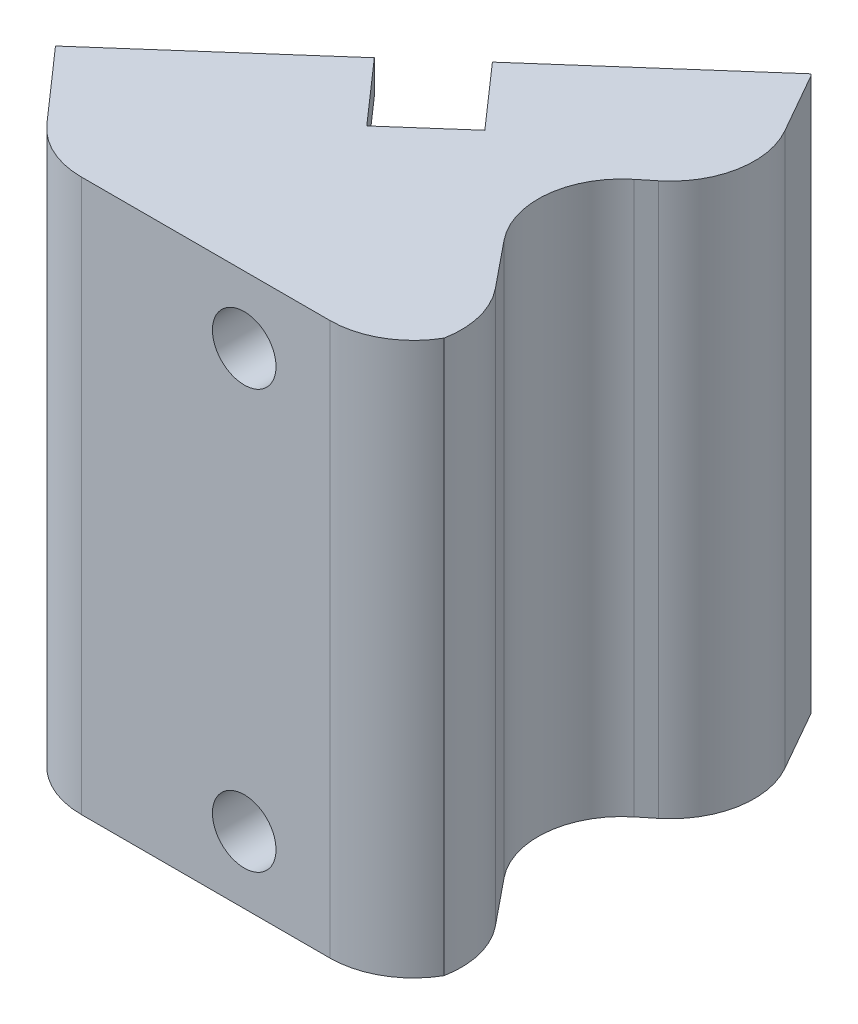
SolidWorks part; units mm, degrees
ref_plane "Front Plane" through (0, 0, 0) normal (0, 0, 1) x (1, 0, 0)
ref_plane "Top Plane" through (0, 0, 0) normal (0, 1, 0) x (1, 0, 0)
ref_plane "Right Plane" through (0, 0, 0) normal (1, 0, 0) x (0, 0, -1)
sketch "Sketch1" plane through (0, 0, 0) normal (0, 1, 0) x (1, 0, 0)
  line L0 (0, 0) -> (20, 0)
  line L1 (20, 0) -> (30.1598, 17.5974)
  line L2 (20, 0) -> (-2.3608, 38.73) construction
  line L3 (0, 0) -> (24.022, 21.141)
  line L4 (30.1598, 17.5974) -> (24.022, 21.141)
  line L5 (20, 0) -> (11.2706, 9.9189) construction
  dimension "D1" = 120
  dimension "D2" = 20
  dimension "D3" = 32
  dimension "D4" = 60
  dimension "D5" = 90
  dimension "D6" = 11.35
extrude "Boss-Extrude1" add sketch "Sketch1" along normal blind 33
sketch "Sketch2" plane through (0, 0, 0) normal (0.6607, 0, 0.7507) x (0.7507, 0, -0.6607)
  line L1 (0, 0) -> (32, 0)
  line L2 (0, 0) -> (0, 33)
  line L3 (0, 33) -> (32, 33)
  line L4 (32, 0) -> (32, 33)
extrude "Boss-Extrude2" add sketch "Sketch2" against normal blind 3
sketch "Sketch3" plane through (30, 0, 0) normal (0, 0, -1) x (-1, 0, 0)
  line L0 (18, -986.4883) -> (18, 49013.5117) construction
  line L1 (-972.5, 16.5) -> (49027.5, 16.5) construction
  line L3 (30, 33) -> (30, 0) construction
  line L4 (30, 33) -> (10, 33) construction
  circle A0 centre (18, 29) radius 1.9
  circle A1 centre (18, 4) radius 1.9
  dimension "D2" = 3.8
  dimension "D3" = 3.8
  dimension "D1" = 12
  dimension "D4" = 12.5
  dimension "D5" = 12.5
  dimension "D6" = 16.5
extrude "Cut-Extrude1" cut sketch "Sketch3" along normal blind 7
fillet "Fillet1" radius 5 1 edges at (20, 16.5, 0)
sketch "Sketch5" plane through (-1.982, 0, -2.2521) normal (-0.6607, 0, -0.7507) x (-0.7507, 0, 0.6607)
  line L0 (-32, 16.5) -> (0, 16.5) construction
  line L3 (-16, 33) -> (-16, 0) construction
  line L8 (0, 33) -> (0, 0) construction
  line L9 (-32, 33) -> (0, 33) construction
  line L10 (0, 0) -> (-32, 0) construction
  line L11 (-32, 33) -> (-32, 0) construction
  circle A0 centre (-28.3, 28.4) radius 2
  circle A1 centre (-3.7, 28.4) radius 2
  circle A2 centre (-28.3, 4.6) radius 2
  circle A3 centre (-3.7, 4.6) radius 2
  dimension "D6" = 4
  dimension "D7" = 4
  dimension "D8" = 4
  dimension "D9" = 4
  dimension "D1" = 12.3
  dimension "D2" = 12.3
  dimension "D3" = 12.3
  dimension "D4" = 12.3
  dimension "D5" = 11.9
  dimension "D10" = 11.9
  dimension "D11" = 11.9
  dimension "D12" = 11.9
extrude "Boss-Extrude3" add sketch "Sketch5" along normal blind 5
sketch "Sketch6" plane through (-1.982, 0, -2.2521) normal (-0.6607, 0, -0.7507) x (-0.7507, 0, 0.6607)
  line L0 (-2, 2) -> (-2, 31)
  line L1 (0, 0) -> (-32, 0)
  line L2 (0, 0) -> (0, 33)
  line L3 (0, 33) -> (-32, 33)
  line L4 (-32, 0) -> (-32, 33)
  line L5 (-2, 31) -> (-30, 31)
  line L6 (-30, 2) -> (-30, 31)
  line L7 (-2, 2) -> (-30, 2)
  dimension "D1" = 2
extrude "Boss-Extrude4" add sketch "Sketch6" along normal blind 5
sketch "Sketch9" plane through (-1.982, 0, -2.2521) normal (-0.6607, 0, -0.7507) x (-0.7507, 0, 0.6607)
  line L0 (-28.3, 26.4) -> (-30, 26.4)
  line L3 (-30, 27.3464) -> (-30, 5.6536) construction
  line L5 (-30, 26.4) -> (-30, 31)
  line L7 (-30, 31) -> (-26.3, 31)
  line L8 (-2, 31) -> (-30, 31) construction
  line L9 (-26.3, 31) -> (-26.3, 28.4)
  line L10 (-26.3, 28.4) -> (-28.3, 26.4)
  line L11 (-5.7, 28.4) -> (-5.7, 31)
  line L13 (-5.7, 31) -> (-2, 31)
  line L14 (-2, 31) -> (-2, 26.4)
  line L15 (-2, 5.6536) -> (-2, 27.3464) construction
  line L17 (-2, 26.4) -> (-3.7, 26.4)
  line L18 (-3.7, 26.4) -> (-5.7, 28.4)
  line L20 (-3.7, 6.6) -> (-2, 6.6)
  line L21 (-2, 5.6536) -> (-2, 27.3464) construction
  line L22 (-2, 6.6) -> (-2, 2)
  line L24 (-2, 2) -> (-5.7, 2)
  line L25 (-30, 2) -> (-2, 2) construction
  line L27 (-5.7, 2) -> (-5.7, 4.6)
  line L28 (-5.7, 4.6) -> (-3.7, 6.6)
  line L29 (-28.3, 6.6) -> (-30, 6.6)
  line L30 (-30, 6.6) -> (-30, 2)
  line L31 (-30, 2) -> (-26.3, 2)
  line L32 (-26.3, 2) -> (-26.3, 4.6)
  line L33 (-26.3, 4.6) -> (-28.3, 6.6)
  arc A9 (-30, 27.3464) -> (-30, 29.4536) centre (-28.3, 28.4) ccw construction
  arc A10 (-30, 27.3464) -> (-30, 29.4536) centre (-28.3, 28.4) ccw construction
  arc A11 (-2, 29.4536) -> (-2, 27.3464) centre (-3.7, 28.4) ccw construction
  arc A12 (-2, 29.4536) -> (-2, 27.3464) centre (-3.7, 28.4) ccw construction
  arc A13 (-2, 5.6536) -> (-2, 3.5464) centre (-3.7, 4.6) ccw construction
  arc A14 (-2, 5.6536) -> (-2, 3.5464) centre (-3.7, 4.6) ccw construction
  arc A15 (-30, 3.5464) -> (-30, 5.6536) centre (-28.3, 4.6) ccw construction
  arc A16 (-30, 3.5464) -> (-30, 5.6536) centre (-28.3, 4.6) ccw construction
extrude "Boss-Extrude5" add sketch "Sketch9" along normal blind 5
sketch "Sketch7" plane through (-5.2853, 0, -6.0055) normal (-0.6607, 0, -0.7507) x (-0.7507, 0, 0.6607)
  line L2 (-5.7, 31) -> (-26.3, 31) construction
  line L3 (-18.5, 90.844) -> (-13.5, 90.844)
  line L4 (-18.5, 90.844) -> (-18.5, -28.844)
  line L5 (-18.5, -28.844) -> (-13.5, -28.844)
  line L6 (-13.5, 90.844) -> (-13.5, -28.844)
  line L8 (-18.5, 90.844) -> (-13.5, -28.844) construction
  line L9 (-18.5, -28.844) -> (-13.5, 90.844) construction
  circle A0 centre (-28.3, 28.4) radius 0.75
  circle A1 centre (-3.7, 28.4) radius 0.75
  circle A2 centre (-3.7, 4.6) radius 0.75
  circle A3 centre (-28.3, 4.6) radius 0.75
  point P0 (-16, 31)
  dimension "D3" = 1.5
  dimension "D4" = 1.5
  dimension "D5" = 1.5
  dimension "D6" = 1.5
  dimension "D1" = 5
extrude "Cut-Extrude3" cut sketch "Sketch7" against normal blind 5
sketch "Sketch8" plane through (0, 33, 0) normal (0, 1, 0) x (1, 0, 0)
  line L0 (17.7453, 28.95) -> (16.8781, 39.6256)
  line L1 (16.8781, 39.6256) -> (45.2125, 18.1015)
  line L2 (45.2125, 18.1015) -> (33.0366, 2.0731)
  line L3 (17.7453, 28.95) -> (33.0366, 2.0731)
extrude "Cut-Extrude4" cut sketch "Sketch8" against normal through all
sketch "Sketch10" plane through (0, 33, 0) normal (0, 1, 0) x (1, 0, 0)
  line L0 (22.9975, 19.7185) -> (15.018, 13.2412)
  line L1 (18.8348, 27.0351) -> (27.1602, 12.4018) construction
  line L2 (15.018, 13.2412) -> (22.3967, 4.1513)
  line L3 (21.4434, 2.5) -> (27.1602, 12.4018) construction
  line L4 (22.3967, 4.1513) -> (32.809, 12.6034)
  line L5 (32.809, 12.6034) -> (22.9975, 19.7185)
extrude "Cut-Extrude5" cut sketch "Sketch10" against normal through all
fillet "Fillet4" radius 5 4 edges at (22.3967, 16.5, -4.1513) (15.018, 16.5, -13.2412) (22.9975, 16.5, -19.7185) (0, 16.5, 0)
equation "\"D2@Sketch5\"=\"D1@Sketch5\""
equation "\"D3@Sketch5\"=\"D1@Sketch5\""
equation "\"D4@Sketch5\"=\"D1@Sketch5\""
equation "\"D7@Sketch5\"=\"D6@Sketch5\""
equation "\"D9@Sketch5\"=\"D6@Sketch5\""
equation "\"D8@Sketch5\"=\"D6@Sketch5\""
equation "\"D10@Sketch5\"=\"D5@Sketch5\""
equation "\"D11@Sketch5\"=\"D5@Sketch5\""
equation "\"D12@Sketch5\"=\"D5@Sketch5\""
